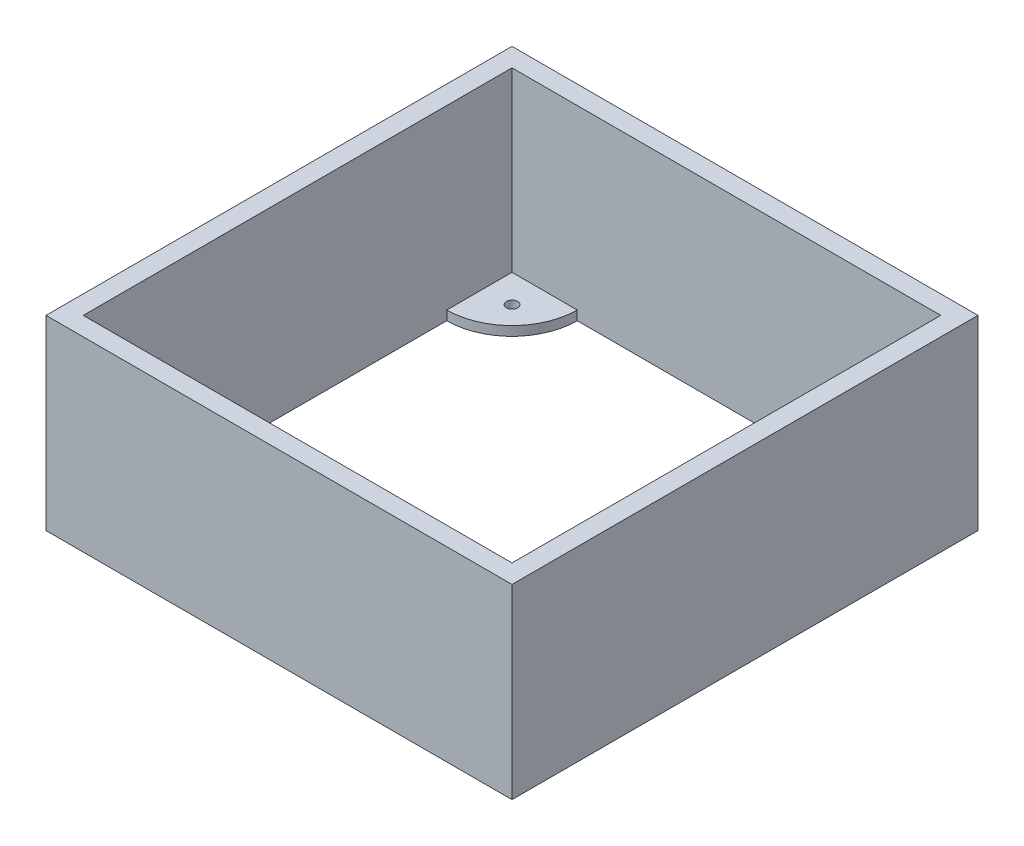
SolidWorks part; units mm, degrees
ref_plane "Front Plane" through (0, 0, 0) normal (0, 0, 1) x (1, 0, 0)
ref_plane "Top Plane" through (0, 0, 0) normal (0, 1, 0) x (1, 0, 0)
ref_plane "Right Plane" through (0, 0, 0) normal (1, 0, 0) x (0, 0, -1)
sketch "Sketch1" plane through (0, 0, 0) normal (0, 1, 0) x (1, 0, 0)
  line L1 (-50, -50) -> (50, -50)
  line L2 (-50, -50) -> (-50, 50)
  line L3 (-50, 50) -> (50, 50)
  line L4 (50, -50) -> (50, 50)
  line L5 (-50, -50) -> (50, 50) construction
  line L6 (-50, 50) -> (50, -50) construction
  line L7 (-46, 46) -> (46, 46)
  line L8 (-46, 46) -> (-46, -46)
  line L9 (-46, -46) -> (46, -46)
  line L10 (46, 46) -> (46, -46)
  line L11 (-46, 46) -> (46, -46) construction
  line L12 (-46, -46) -> (46, 46) construction
  point P0 (0, 0)
  point P6 (0, 0)
  dimension "D1" = 4
  dimension "D2" = 100
  dimension "D3" = 100
  dimension "D4" = 92
extrude "Boss-Extrude1" add sketch "Sketch1" along normal blind 40
sketch "Sketch2" plane through (0, 0, 0) normal (0, -1, 0) x (-1, 0, 0)
  line L0 (-46, 32) -> (-46, 46)
  line L1 (-46, 46) -> (-32, 46)
  line L2 (32, 46) -> (46, 46)
  line L3 (46, 46) -> (46, 32)
  line L4 (46, -32) -> (46, -46)
  line L5 (46, -46) -> (32, -46)
  line L6 (-32, -46) -> (-46, -46)
  line L7 (-46, -46) -> (-46, -32)
  arc A0 (-46, 32) -> (-32, 46) centre (-46, 46) ccw
  arc A1 (32, 46) -> (46, 32) centre (46, 46) ccw
  arc A2 (46, -32) -> (32, -46) centre (46, -46) ccw
  arc A3 (-32, -46) -> (-46, -32) centre (-46, -46) ccw
  point P16 (0, 0)
  dimension "D2" = 14
  dimension "D1" = 4
extrude "Boss-Extrude2" add sketch "Sketch2" against normal blind 2
sketch "Sketch3" plane through (0, 0, 0) normal (0, -1, 0) x (-1, 0, 0)
  line L0 (-32, 46) -> (32, 46) construction
  line L1 (-46, -32) -> (-46, 32) construction
  line L2 (46, 32) -> (46, -32) construction
  line L3 (32, -46) -> (-32, -46) construction
  point P0 (-40, 40)
  point P1 (40, 40)
  point P2 (40, -40)
  point P3 (-40, -40)
  dimension "D2" = 6
  dimension "D1" = 6
  dimension "D3" = 6
  dimension "D4" = 6
  dimension "D5" = 6
  dimension "D6" = 6
  dimension "D7" = 6
  dimension "D8" = 6
hole_wizard "M2 Clearance Hole1" positions "3DSketch1" profile "Sketch4" hole size "M2" standard "ANSI Metric" end condition through all
sketch3d "3DSketch1"
  point P0 (40, 0, 40)
  point P3 (40, 0, -40)
  point P6 (-40, 0, -40)
  point P9 (-40, 0, 40)
sketch "Sketch4" plane through (40, 0, 40) normal (1, 0, 0) x (0, 0, -1)
  line L0 (0, 0) -> (0, 40)
  line L1 (0, 40) -> (1.2, 40)
  line L2 (1.2, 40) -> (1.2, 0)
  line L5 (1.2, 0) -> (0, 0)
  line L11 (0, -6.35) -> (0, 107.95) construction
  dimension "Thru Hole Dia." = 2.4
  dimension "Thru Hole Depth" = 40
sketch "Sketch5" plane through (-50, 0, 0) normal (-1, 0, 0) x (0, 0, 1)
  circle A0 centre (0, 0) radius 16.7236
